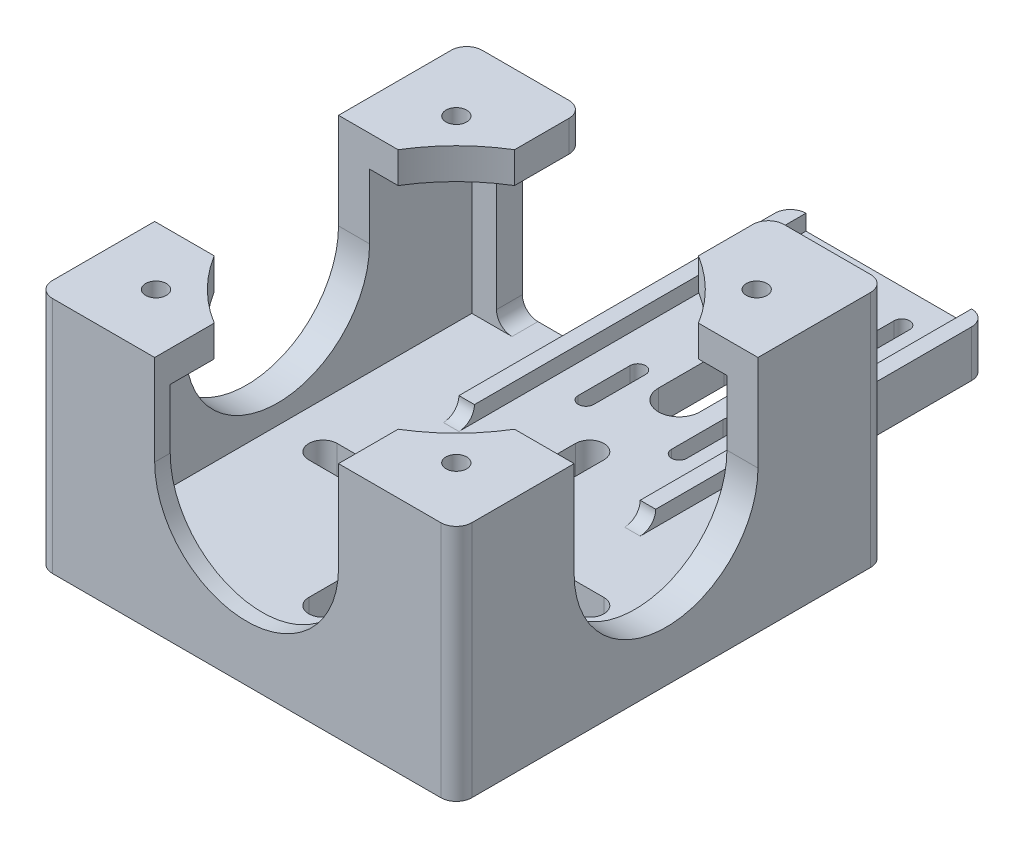
SolidWorks part; units mm, degrees
ref_plane "Front Plane" through (0, 0, 0) normal (0, 0, 1) x (1, 0, 0)
ref_plane "Top Plane" through (0, 0, 0) normal (0, 1, 0) x (1, 0, 0)
ref_plane "Right Plane" through (0, 0, 0) normal (1, 0, 0) x (0, 0, -1)
sketch "Sketch1" plane through (0, 0, 0) normal (0, 0, 1) x (1, 0, 0)
  line L1 (-37.5, 3) -> (37.5, 3)
  line L2 (-37.5, 3) -> (-37.5, -3)
  line L3 (-37.5, -3) -> (37.5, -3)
  line L4 (37.5, 3) -> (37.5, -3)
  line L5 (-37.5, 3) -> (37.5, -3) construction
  line L6 (-37.5, -3) -> (37.5, 3) construction
  line L7 (37.5, -3) -> (43.5, -3)
  line L8 (37.5, -3) -> (37.5, 37)
  line L9 (37.5, 37) -> (43.5, 37)
  line L10 (43.5, -3) -> (43.5, 37)
  line L11 (43.5, 37) -> (-37.5, 37)
  line L12 (43.5, 37) -> (43.5, 43)
  line L13 (43.5, 43) -> (-37.5, 43)
  line L14 (-37.5, 37) -> (-37.5, 43)
  point P0 (0, 0)
  dimension "D1" = 75
  dimension "D2" = 6
  dimension "D3" = 40
  dimension "D4" = 6
  dimension "D5" = 6
  dimension "D6" = 81
extrude "Boss-Extrude1" add sketch "Sketch1" against normal blind 75 contours L14 L11 L9 L12 L13 | L7 L10 L9 L8 L4 | L4 L1 L2 L3
sketch "Sketch2" plane through (0, 43, 0) normal (0, 1, 0) x (1, 0, 0)
  line L0 (3, 75) -> (3, 0) construction
  line L1 (43.5, 75) -> (-37.5, 75) construction
  line L2 (43.5, 0) -> (-37.5, 0) construction
  line L4 (-26, 8.5) -> (32, 8.5)
  line L5 (-26, 8.5) -> (-26, 66.5)
  line L6 (-26, 66.5) -> (32, 66.5)
  line L7 (32, 8.5) -> (32, 66.5)
  line L8 (-26, 8.5) -> (32, 66.5) construction
  line L9 (-26, 66.5) -> (32, 8.5) construction
  circle A0 centre (3, 37.5) radius 34
  circle A1 centre (-26, 66.5) radius 2
  circle A2 centre (32, 66.5) radius 2
  circle A3 centre (32, 8.5) radius 2
  circle A4 centre (-26, 8.5) radius 2
  dimension "D1" = 58
  dimension "D2" = 58
extrude "Cut-Extrude1" cut sketch "Sketch2" against normal up to next contours A0 | A4 | A3 | A2 | A1
sketch "Sketch3" plane through (0, -3, 0) normal (0, -1, 0) x (1, 0, 0)
  line L0 (3, 0) -> (3, -75) construction
  line L1 (-37.5, 0) -> (43.5, 0) construction
  line L2 (-37.5, -75) -> (43.5, -75) construction
  circle A0 centre (3, -37.5) radius 3
extrude "Cut-Extrude2" cut sketch "Sketch3" against normal up to next
sketch "Sketch11" plane through (0, -3, 0) normal (0, -1, 0) x (1, 0, 0)
  line L0 (3, -37.5) -> (3, -80.5387)
  line L2 (3, -80.5387) -> (3, -93.222) construction
  line L5 (7, -80.5387) -> (7, -93.222)
  line L12 (-1, -80.5387) -> (-1, -93.222)
  line L15 (-6, -71.5387) -> (-6, -81.5387) construction
  line L16 (3, -80.5387) -> (-6, -80.5387)
  line L17 (3, -80.5387) -> (3, -71.5387)
  line L18 (3, -71.5387) -> (-6, -71.5387)
  line L19 (-6, -80.5387) -> (-6, -71.5387)
  line L20 (-4.5, -71.5387) -> (-4.5, -81.5387)
  line L21 (-7.5, -71.5387) -> (-7.5, -81.5387)
  line L22 (12, -71.5387) -> (12, -81.5387) construction
  line L23 (10.5, -71.5387) -> (10.5, -81.5387)
  line L24 (13.5, -71.5387) -> (13.5, -81.5387)
  line L25 (-6, -104.5387) -> (-6, -114.5387) construction
  line L26 (-4.5, -104.5387) -> (-4.5, -114.5387)
  line L27 (-7.5, -104.5387) -> (-7.5, -114.5387)
  line L28 (12, -104.5387) -> (12, -114.5387) construction
  line L29 (10.5, -104.5387) -> (10.5, -114.5387)
  line L30 (13.5, -104.5387) -> (13.5, -114.5387)
  line L31 (-37.5, -75) -> (43.5, -75) construction
  line L32 (-16, -75) -> (22, -75)
  line L33 (3, -75) -> (3, -121)
  line L34 (-16, -121) -> (22, -121)
  line L35 (22, -75) -> (22, -121)
  line L36 (-16, -75) -> (-16, -121)
  arc A6 (7, -80.5387) -> (-1, -80.5387) centre (3, -80.5387) ccw
  arc A7 (-1, -93.222) -> (7, -93.222) centre (3, -93.222) ccw
  arc A8 (-4.5, -71.5387) -> (-7.5, -71.5387) centre (-6, -71.5387) ccw
  arc A9 (-7.5, -81.5387) -> (-4.5, -81.5387) centre (-6, -81.5387) ccw
  arc A10 (10.5, -71.5387) -> (13.5, -71.5387) centre (12, -71.5387) cw
  arc A11 (13.5, -81.5387) -> (10.5, -81.5387) centre (12, -81.5387) cw
  arc A12 (-4.5, -104.5387) -> (-7.5, -104.5387) centre (-6, -104.5387) ccw
  arc A13 (-7.5, -114.5387) -> (-4.5, -114.5387) centre (-6, -114.5387) ccw
  arc A14 (10.5, -104.5387) -> (13.5, -104.5387) centre (12, -104.5387) cw
  arc A15 (13.5, -114.5387) -> (10.5, -114.5387) centre (12, -114.5387) cw
  point P3 (3, -86.8804)
  point P13 (-6, -76.5387)
  point P21 (12, -76.5387)
  point P29 (-6, -109.5387)
  point P39 (12, -109.5387)
  line M36 (-37.5, -75) -> (43.5, -75)
  dimension "D1" = 9
  dimension "D3" = 2
  dimension "D2" = 9
  dimension "D4" = 19
  dimension "D5" = 46
extrude "Boss-Extrude5" add sketch "Sketch11" against normal blind 6 contours A9 L21 L36 L34 L33 A7 L12 L16 L20 A13 L27 A12 L26 M36 | L24 A11 L23 L0 A6 L5 A7 L33 L34 L35 L30 A15 L29 A14 M36 | A6 L0 L20 L16 M36
sketch "Sketch12" plane through (0, -3, 0) normal (0, -1, 0) x (1, 0, 0)
  line L0 (-6, -81.5387) -> (-6, -71.5387) construction
  line L1 (-7.5, -81.5387) -> (-7.5, -71.5387)
  line L2 (-4.5, -81.5387) -> (-4.5, -71.5387)
  line L3 (3, -80.5387) -> (3, -68.2941) construction
  line L4 (12, -81.5387) -> (12, -71.5387) construction
  line L5 (13.5, -81.5387) -> (13.5, -71.5387)
  line L6 (10.5, -81.5387) -> (10.5, -71.5387)
  arc A0 (-7.5, -81.5387) -> (-4.5, -81.5387) centre (-6, -81.5387) ccw
  arc A1 (-4.5, -71.5387) -> (-7.5, -71.5387) centre (-6, -71.5387) ccw
  arc A2 (13.5, -81.5387) -> (10.5, -81.5387) centre (12, -81.5387) cw
  arc A3 (10.5, -71.5387) -> (13.5, -71.5387) centre (12, -71.5387) cw
  point P3 (-6, -76.5387)
  point P13 (12, -76.5387)
extrude "Cut-Extrude3" cut sketch "Sketch12" against normal up to next
sketch "Sketch14" plane through (0, 0, -121) normal (0, 0, -1) x (-1, 0, 0)
  line L0 (-3, 3) -> (-3, 22.5331) construction
  line L1 (-22, 3) -> (-19, 3)
  line L2 (-22, 3) -> (-22, 6)
  line L3 (-22, 6) -> (-19, 6)
  line L4 (-19, 3) -> (-19, 6)
  line L5 (16, 3) -> (-22, 3) construction
  line L6 (16, 6) -> (13, 6)
  line L7 (13, 3) -> (13, 6)
  line L8 (16, 3) -> (13, 3)
  line L9 (16, 3) -> (16, 6)
  dimension "D1" = 3
  dimension "D2" = 3
extrude "Boss-Extrude6" add sketch "Sketch14" against normal blind 64
sketch "Sketch15" plane through (0, 0, 0) normal (0, 0, 1) x (1, 0, 0)
  line L1 (-37.5, 43) -> (43.5, 43)
  line L2 (-37.5, 43) -> (-37.5, -3)
  line L3 (-37.5, -3) -> (43.5, -3)
  line L4 (43.5, 43) -> (43.5, -3)
extrude "Boss-Extrude7" add sketch "Sketch15" along normal blind 3
fillet "Fillet6" radius 3 1 edges at (43.5, 20, 3)
fillet "Fillet7" radius 3 1 edges at (-37.5, 20, 3)
fillet "Fillet9" radius 3 2 edges at (20.5, 6, -121) (22, 1.5, -121)
fillet "Fillet10" radius 3 2 edges at (-14.5, 6, -121) (-16, 1.5, -121)
fillet "Fillet11" radius 3 3 edges at (-16, 4.5, -57) (-14.5, 3, -57) (-13, 4.5, -57)
fillet "Fillet12" radius 3 3 edges at (22, 4.5, -57) (19, 4.5, -57) (20.5, 3, -57)
sketch "Sketch22" plane through (0, 0, 0) normal (0, 0, -1) x (-1, 0, 0)
  line L0 (37.5, 3) -> (16, 3) construction
  line L1 (37.5, 37) -> (31.5, 37)
  line L2 (37.5, 37) -> (37.5, 3)
  line L3 (37.5, 3) -> (31.5, 3)
  line L4 (31.5, 37) -> (31.5, 3)
  dimension "D1" = 6
extrude "Boss-Extrude9" add sketch "Sketch22" along normal blind 75
fillet "Fillet13" radius 3 1 edges at (3, 3, 0)
sketch "Sketch26" plane through (0, -3, 0) normal (0, -1, 0) x (1, 0, 0)
  line L0 (3, -37.5) -> (3, -76.5387) construction
  line L1 (3, -50.7929) -> (3, -63.2458) construction
  line L2 (5.7491, -50.7929) -> (5.7491, -63.2458)
  line L3 (0.2509, -50.7929) -> (0.2509, -63.2458)
  line L4 (-10.2929, -37.5) -> (-22.7458, -37.5) construction
  line L5 (-10.2929, -40.2491) -> (-22.7458, -40.2491)
  line L6 (-10.2929, -34.7509) -> (-22.7458, -34.7509)
  line L7 (3, -24.2071) -> (3, -11.7542) construction
  line L8 (0.2509, -24.2071) -> (0.2509, -11.7542)
  line L9 (5.7491, -24.2071) -> (5.7491, -11.7542)
  line L10 (16.2929, -37.5) -> (28.7458, -37.5) construction
  line L11 (16.2929, -34.7509) -> (28.7458, -34.7509)
  line L12 (16.2929, -40.2491) -> (28.7458, -40.2491)
  arc A0 (7, -80.5387) -> (-1, -80.5387) centre (3, -80.5387) ccw construction
  arc A1 (5.7491, -50.7929) -> (0.2509, -50.7929) centre (3, -50.7929) ccw
  arc A2 (0.2509, -63.2458) -> (5.7491, -63.2458) centre (3, -63.2458) ccw
  arc A3 (-10.2929, -40.2491) -> (-10.2929, -34.7509) centre (-10.2929, -37.5) ccw
  arc A4 (-22.7458, -34.7509) -> (-22.7458, -40.2491) centre (-22.7458, -37.5) ccw
  arc A5 (0.2509, -24.2071) -> (5.7491, -24.2071) centre (3, -24.2071) ccw
  arc A6 (5.7491, -11.7542) -> (0.2509, -11.7542) centre (3, -11.7542) ccw
  arc A7 (16.2929, -34.7509) -> (16.2929, -40.2491) centre (16.2929, -37.5) ccw
  arc A8 (28.7458, -40.2491) -> (28.7458, -34.7509) centre (28.7458, -37.5) ccw
  point P8 (3, -57.0194)
  point P18 (-16.5194, -37.5)
  point P25 (3, -17.9806)
  point P32 (22.5194, -37.5)
  dimension "D1" = 4
extrude "Cut-Extrude8" cut sketch "Sketch26" against normal up to next
sketch "Sketch29" plane through (0, 43, 0) normal (0, 1, 0) x (1, 0, 0)
  line L0 (-26, 37.5) -> (-37.5, 37.5)
  line L1 (-26, 19.7518) -> (-26, 55.2482) construction
  line L2 (-37.5, 75) -> (-37.5, 0) construction
sketch "Sketch30" plane through (-37.5, 0, 0) normal (-1, 0, 0) x (0, 0, 1)
  line L0 (-37.5, 61.5) -> (-37.5, 24.5) construction
  line L1 (-75, 43) -> (0, 43) construction
  line L2 (-19.75, 61.5) -> (-19.75, 24.5)
  line L3 (-55.25, 61.5) -> (-55.25, 24.5)
  arc A0 (-19.75, 61.5) -> (-55.25, 61.5) centre (-37.5, 61.5) ccw
  arc A1 (-55.25, 24.5) -> (-19.75, 24.5) centre (-37.5, 24.5) ccw
  point P5 (-37.5, 43)
extrude "Cut-Extrude10" cut sketch "Sketch30" against normal through all contours L3 A1 L2 A0
sketch "Sketch31" plane through (0, 0, 3) normal (0, 0, 1) x (1, 0, 0)
  line L0 (3, 60.5) -> (3, 25.5) construction
  line L1 (40.5, 43) -> (-34.5, 43) construction
  line L2 (20.75, 60.5) -> (20.75, 25.5)
  line L3 (-14.75, 60.5) -> (-14.75, 25.5)
  arc A0 (20.75, 60.5) -> (-14.75, 60.5) centre (3, 60.5) ccw
  arc A1 (-14.75, 25.5) -> (20.75, 25.5) centre (3, 25.5) ccw
  point P4 (3, 43)
extrude "Cut-Extrude11" cut sketch "Sketch31" against normal through all
sketch "Sketch35" plane through (0, 0, -75) normal (0, 0, -1) x (-1, 0, 0)
  line L0 (-20.75, 37) -> (-20.75, 43)
  line L1 (-20.75, 43) -> (-43.5, 43)
  line L2 (-43.5, 43) -> (-43.5, -3)
  line L3 (-43.5, -3) -> (-22, -3)
  line L4 (-22, -3) -> (-22, 3)
  line L5 (-22, 3) -> (-32.75, 3)
  line L6 (31.5, 3) -> (-37.5, 3) construction
  line L7 (-32.75, 3) -> (-32.75, 37)
  line L8 (-37.5, 37) -> (-20.75, 37) construction
  line L9 (-32.75, 37) -> (-20.75, 37)
  line L10 (-3, 25.5) -> (-3, 0) construction
  line L11 (26.75, 3) -> (26.75, 37)
  line L12 (16, 3) -> (26.75, 3)
  line L13 (16, -3) -> (16, 3)
  line L14 (37.5, -3) -> (16, -3)
  line L15 (37.5, 43) -> (37.5, -3)
  line L16 (14.75, 43) -> (37.5, 43)
  line L17 (14.75, 37) -> (14.75, 43)
  line L18 (26.75, 37) -> (14.75, 37)
extrude "Boss-Extrude12" add sketch "Sketch35" along normal blind 5
fillet "Fillet28" radius 3 1 edges at (-37.5, 20, -80)
fillet "Fillet29" radius 3 1 edges at (43.5, 20, -80)
fillet "Fillet30" radius 3 1 edges at (20.75, 40, -80)
fillet "Fillet31" radius 3 1 edges at (-14.75, 40, -80)
fillet "Fillet32" radius 3 1 edges at (-26.75, 3, -77.5)
fillet "Fillet33" radius 3 1 edges at (32.75, 3, -77.5)
